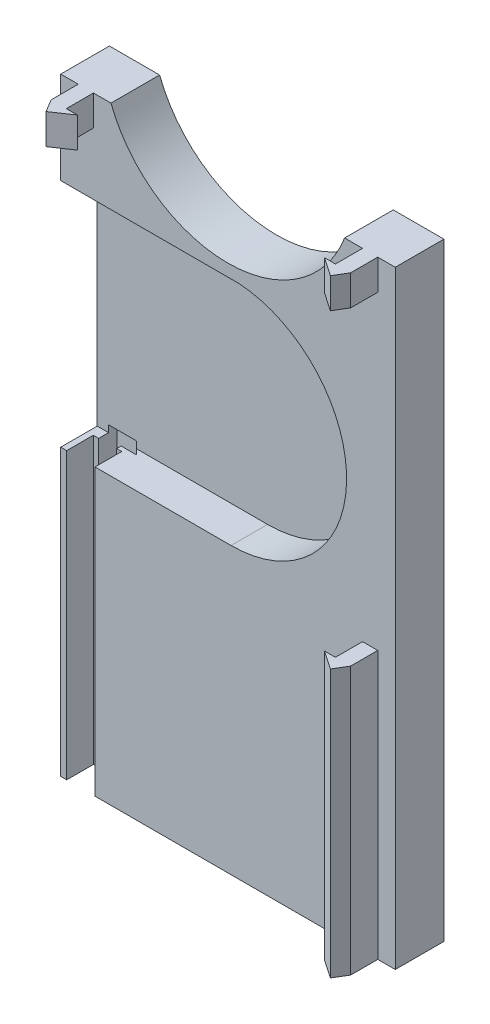
SolidWorks part; units mm, degrees
ref_plane "Front Plane" through (0, 0, 0) normal (0, 0, 1) x (1, 0, 0)
ref_plane "Top Plane" through (0, 0, 0) normal (0, 1, 0) x (1, 0, 0)
ref_plane "Right Plane" through (0, 0, 0) normal (1, 0, 0) x (0, 0, -1)
sketch "Sketch1" plane through (0, 0, 0) normal (0, 1, 0) x (1, 0, 0)
  line L1 (27.5, 4) -> (-27.5, 4)
  line L2 (27.5, 4) -> (27.5, -4)
  line L3 (27.5, -4) -> (-27.5, -4)
  line L4 (-27.5, 4) -> (-27.5, -4)
  line L5 (27.5, 4) -> (-27.5, -4) construction
  line L6 (27.5, -4) -> (-27.5, 4) construction
  point P0 (0, 0)
  dimension "D1" = 55
  dimension "D2" = 8
extrude "Boss-Extrude1" add sketch "Sketch1" along normal blind 100
sketch "Sketch6" plane through (-27.5, 0, 0) normal (-1, 0, 0) x (0, 0, 1)
  line L0 (4, 100) -> (4, 0) construction
  line L1 (4, 84.832) -> (-2, 84.832)
  line L2 (4, 84.832) -> (4, 46.8798)
  line L3 (4, 46.8798) -> (-2, 46.8798)
  line L4 (-2, 84.832) -> (-2, 46.8798)
  dimension "D1" = 6
extrude "Cut-Extrude1" cut sketch "Sketch6" against normal blind 47
sketch "Sketch7" plane through (0, 0, 0) normal (0, -1, 0) x (1, 0, 0)
  line L0 (-27.5, 4) -> (27.5, 4) construction
  line L1 (-26.519, 4) -> (-21.8692, 4)
  line L2 (-26.519, 4) -> (-26.519, -0.3737)
  line L4 (-21.8692, 4) -> (-21.8692, -0.3928)
  line L5 (-24.0978, 1.0006) -> (-24.0978, -3.4126) construction
  line L15 (-25.6317, -3.4126) -> (-22.4044, -3.3598)
  line L16 (-22.4044, -3.3598) -> (-20.2109, -1.1277)
  line L17 (-20.2109, -1.1277) -> (-22.6978, -1.1277)
  line L18 (-22.6978, -1.1277) -> (-22.6978, -0.3928)
  line L19 (-26.519, -0.3737) -> (-25.6317, -0.3737)
  line L20 (-22.6978, -0.3928) -> (-21.8692, -0.3928)
  line L21 (-25.6317, -0.3737) -> (-25.6317, -3.4126)
  point P6 (-24.7808, 1.3349)
extrude "Cut-Extrude2" cut sketch "Sketch7" against normal blind 48
sketch "Sketch8" plane through (0, 0, -4) normal (0, 0, -1) x (-1, 0, 0)
  line L0 (-27.5, 100) -> (27.5, 100) construction
  line L1 (-19.1716, 100) -> (19.2439, 100)
  arc A0 (-19.1716, 100) -> (19.2439, 100) centre (0.0361, 107.4128) ccw
extrude "Cut-Extrude3" cut sketch "Sketch8" against normal blind 8
sketch "Sketch9" plane through (0, 100, 0) normal (0, 1, 0) x (1, 0, 0)
  line L0 (-27.5, -4) -> (-19.2439, -4) construction
  line L1 (-22.122, 0.4626) -> (-24.622, 0.4626)
  line L2 (-22.122, 0.4626) -> (-22.122, -8.4626)
  line L4 (-24.622, 0.4626) -> (-24.622, -8.4626)
  line L5 (-23.372, 0.4626) -> (-23.372, -10.5374) construction
  line L8 (-23.372, -10.5374) -> (-20.322, -8.4626)
  line L9 (-20.322, -8.4626) -> (-22.122, -8.4626)
  line L10 (-24.622, -8.4626) -> (-23.372, -10.5374)
  line L11 (0, 0) -> (0, -5.3623) construction
  line L12 (24.622, -8.4626) -> (23.372, -10.5374)
  line L13 (23.372, -10.5374) -> (20.322, -8.4626)
  line L14 (20.322, -8.4626) -> (22.122, -8.4626)
  line L15 (22.122, 0.4626) -> (22.122, -8.4626)
  line L16 (22.122, 0.4626) -> (24.622, 0.4626)
  line L17 (24.622, 0.4626) -> (24.622, -8.4626)
  point P0 (-23.372, -4)
  dimension "D1" = 2.5
  dimension "D2" = 1.8
  dimension "D4" = 11
extrude "Boss-Extrude2" add sketch "Sketch9" against normal blind 5
sketch "Sketch10" plane through (0, 100, 0) normal (0, 1, 0) x (1, 0, 0)
  line L0 (0, 0) -> (0, -8.497) construction
sketch "Sketch11" plane through (0, 0, -2) normal (0, 0, 1) x (1, 0, 0)
  line L0 (19.5, 84.832) -> (19.5, 46.8798) construction
  line L2 (19.5, 46.8798) -> (-21.0681, 46.8798) construction
  line L7 (-27.5, 84.832) -> (-27.5, 46.8798)
  line L8 (-27.5, 46.8798) -> (-25.6317, 46.8798)
  line L9 (19.5, 46.8798) -> (19.5, 84.832)
  line L10 (19.5, 84.832) -> (-27.5, 84.832)
  line L12 (0.5, 46.8798) -> (-25.6317, 46.8798)
  line L13 (19.5, 46.8798) -> (19.5, 84.832)
  line L14 (19.5, 84.832) -> (-0.8467, 84.832)
  line L19 (-25.6317, 48) -> (-21.0681, 48)
  line L20 (-25.6317, 48) -> (-21.0681, 48)
  line L21 (-21.0681, 48) -> (-21.0681, 46.8798)
  line L22 (-21.0681, 48) -> (-21.0681, 46.8798)
  line L23 (-21.0681, 46.8798) -> (19.5, 46.8798)
  line L24 (-21.0681, 46.8798) -> (19.5, 46.8798)
  line L25 (-25.6317, 46.8798) -> (-25.6317, 48)
  line L26 (-25.6317, 46.8798) -> (-25.6317, 48)
  arc A0 (0.5, 46.8798) -> (-0.8467, 84.832) centre (0.5, 65.8798) ccw
  line M7 (-27.5, 46.8798) -> (-25.6317, 46.8798)
  line M8 (19.5, 46.8798) -> (19.5, 84.832)
  line M9 (19.5, 84.832) -> (-27.5, 84.832)
  dimension "D1" = 38
  dimension "D2" = 0
extrude "Boss-Extrude3" add sketch "Sketch11" along normal blind 6 contours A0 L13 M9 | A0 M7 M8 region at (15.3103, 80.5881, -2) region at (15.256, 51.1238, -2)
sketch "Sketch12" plane through (0, 0, 0) normal (0, -1, 0) x (1, 0, 0)
  line L0 (24.622, 8.4626) -> (24.622, 4) construction
  line L1 (23.372, 10.5374) -> (24.622, 8.4626) construction
  line L2 (20.322, 8.4626) -> (23.372, 10.5374) construction
  line L3 (22.122, 8.4626) -> (20.322, 8.4626) construction
  line L4 (22.122, 4) -> (22.122, 8.4626) construction
  line L5 (-22.122, 8.4626) -> (-22.122, 4) construction
  line L6 (-20.322, 8.4626) -> (-22.122, 8.4626) construction
  line L7 (-23.372, 10.5374) -> (-20.322, 8.4626) construction
  line L8 (-24.622, 8.4626) -> (-23.372, 10.5374) construction
  line L9 (-24.622, 4) -> (-24.622, 8.4626) construction
  line L10 (24.622, 8.4626) -> (24.622, 4)
  line L11 (23.372, 10.5374) -> (24.622, 8.4626)
  line L12 (20.322, 8.4626) -> (23.372, 10.5374)
  line L13 (22.122, 8.4626) -> (20.322, 8.4626)
  line L14 (22.122, 4) -> (22.122, 8.4626)
  line L15 (-22.122, 8.4626) -> (-22.122, 4)
  line L16 (-20.322, 8.4626) -> (-22.122, 8.4626)
  line L17 (-23.372, 10.5374) -> (-20.322, 8.4626)
  line L18 (-24.622, 8.4626) -> (-23.372, 10.5374)
  line L19 (-24.622, 4) -> (-24.622, 8.4626)
  line L20 (24.622, 4) -> (22.122, 4)
  line L21 (-22.122, 4) -> (-24.622, 4)
  line M4 (27.5, 4) -> (-21.8692, 4)
extrude "Boss-Extrude4" add sketch "Sketch12" against normal blind 44 separate body contours L14 L10 L11 L12 L13 M4 region at (23.2006, 0, 7.0662)
